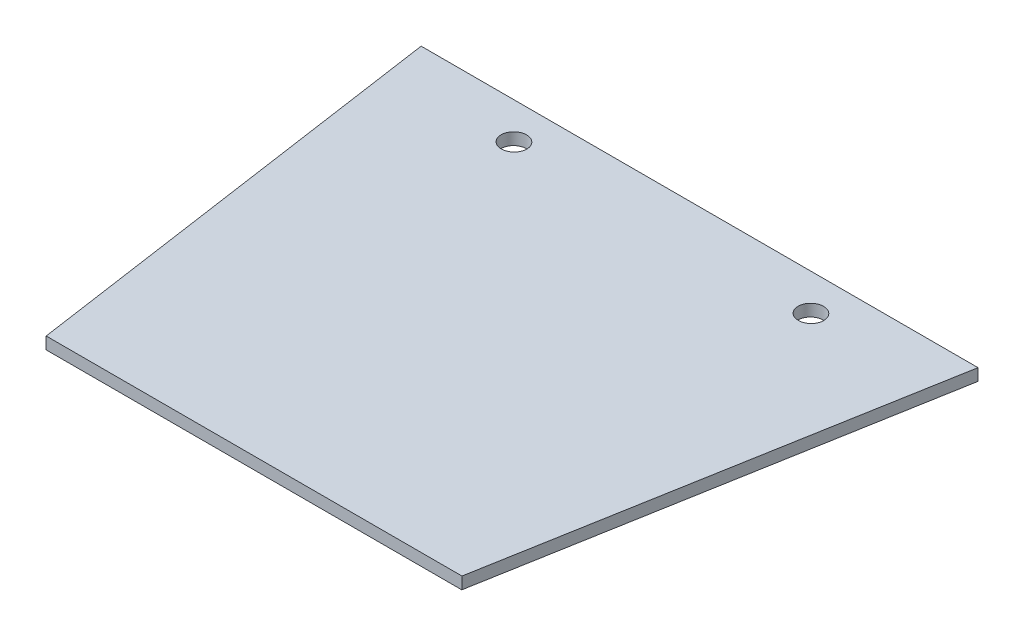
SolidWorks part; units mm, degrees
ref_plane "Front Plane" through (0, 0, 0) normal (0, 0, 1) x (1, 0, 0)
ref_plane "Top Plane" through (0, 0, 0) normal (0, 1, 0) x (1, 0, 0)
ref_plane "Right Plane" through (0, 0, 0) normal (1, 0, 0) x (0, 0, -1)
sketch "Sketch1" plane through (0, -24.2237, 0.3811) normal (0, -0.9999, 0.0157) x (-1, 0, 0)
  line L0 (-37.5, 49.3522) -> (-28, -10.6552)
  line L1 (-28, -10.6552) -> (28, -10.6552)
  line L2 (28, -10.6552) -> (37.5, 49.3522)
  line L3 (37.5, 49.3522) -> (-37.5, 49.3522)
extrude "Boss-Extrude1" add sketch "Sketch1" along normal blind 1.6
sketch "Front Mounting Holes" plane through (0, -25.8235, 0.4063) normal (0, -0.9999, 0.0157) x (1, 0, 0)
  line L0 (0, 0) -> (0, -50000) construction
  line L1 (-20, -44.3522) -> (20, -44.3522) construction
  line L2 (-37.5, -49.3522) -> (37.5, -49.3522) construction
  circle A0 centre (20, -44.3522) radius 1.7
  circle A1 centre (-20, -44.3522) radius 1.7
  point P6 (0, -44.3522)
  dimension "D1" = 3.4
  dimension "D2" = 3.4
  dimension "D3" = 20
  dimension "D4" = 5
extrude "Cut-Extrude1" cut sketch "Front Mounting Holes" against normal through all
sketch "PCB Sketch" plane through (0, -24.2237, 0.3811) normal (0, 0.9999, -0.0157) x (1, 0, 0)
  line L4 (37.5, 49.3522) -> (-37.5, 49.3522)
  line L5 (-37.5, 49.3522) -> (-28, -10.6552)
  line L6 (-28, -10.6552) -> (28, -10.6552)
  line L7 (28, -10.6552) -> (37.5, 49.3522)
  line L8 (37.5, 49.3522) -> (-37.5, 49.3522)
  line L9 (-37.5, 49.3522) -> (-28, -10.6552)
  line L10 (-28, -10.6552) -> (28, -10.6552)
  line L11 (28, -10.6552) -> (37.5, 49.3522)
  circle A0 centre (20, 44.3522) radius 1.7 construction
  circle A1 centre (-20, 44.3522) radius 1.7 construction
  circle A2 centre (20, 44.3522) radius 1.7
  circle A3 centre (-20, 44.3522) radius 1.7
  dimension "D1" = 0
